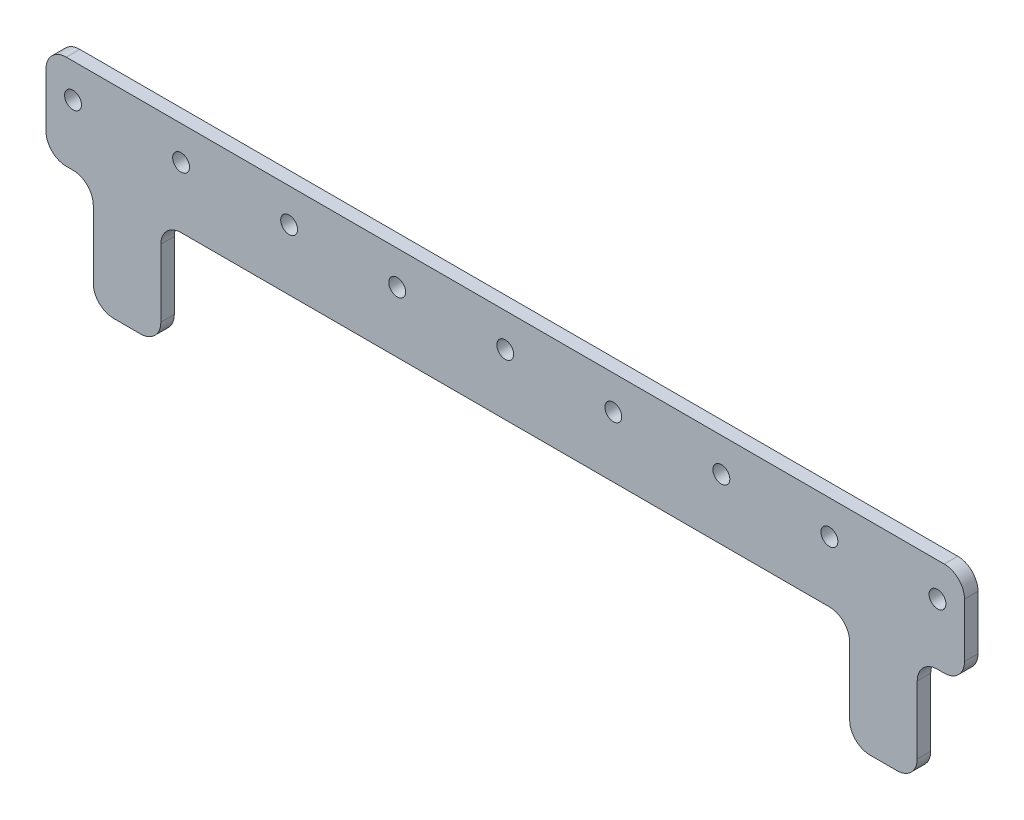
SolidWorks part; units mm, degrees
ref_plane "Top" through (0, 0, 0) normal (0, 0, 1) x (1, 0, 0)
ref_plane "Front" through (0, 0, 0) normal (0, 1, 0) x (1, 0, 0)
ref_plane "Right" through (0, 0, 0) normal (1, 0, 0) x (0, 0, -1)
sketch "Base Sketch" plane through (0, 0, 0) normal (0, 0, 1) x (1, 0, 0)
  line L0 (-68, 7) -> (68, -7) construction
  line L1 (-68, 7) -> (68, 7)
  line L2 (-68, 7) -> (-68, -7)
  line L3 (-68, -7) -> (68, -7)
  line L4 (68, 7) -> (68, -7)
  point P4 (0, 0)
  dimension "Length" = 136
  dimension "D2" = 14
extrude "Base Extrude" add sketch "Base Sketch" against normal blind 2
sketch "Pin Hole Sketch" plane through (0, 0, 0) normal (0, 0, 1) x (1, 0, 0)
  line L0 (68, -7) -> (68, 7) construction
  line L1 (68, 7) -> (-68, 7) construction
  circle A0 centre (64, 2) radius 1.25
  dimension "Diameter" = 2.5
  dimension "D1" = 4
  dimension "D2" = 5
extrude "First Pin Hole Cut" cut sketch "Pin Hole Sketch" against normal through all
pattern_linear "Pin Hole Pattern" count 9 spacing 16 along (-1, 0, 0) of "First Pin Hole Cut"
sketch "Extension Sketch" plane through (0, 0, 0) normal (0, 0, 1) x (1, 0, 0)
  line L0 (48, 2) -> (64, 2) construction
  line L1 (56, 2) -> (56, -23) construction
  line L2 (51, -23) -> (61, -23)
  line L3 (61, -23) -> (61, 2)
  line L4 (61, 2) -> (51, 2)
  line L5 (51, 2) -> (51, -23)
  line L6 (68, 7) -> (-68, 7) construction
  circle A0 centre (64, 2) radius 1.25 construction
  circle A1 centre (48, 2) radius 1.25 construction
  dimension "D1" = 10
  dimension "D2" = 30
extrude "Tab Extrude" add sketch "Extension Sketch" against normal through all separate body
mirror "Tab Mirror" about plane through (0, 0, 0) normal (1, 0, 0) of "Tab Extrude"
combine bodies "Combine Bodies" operation type add bodies to combine 106 105
fillet "Corner Fillets" radius 3 12 edges at (68, 7, -1) (68, -7, -1) (-68, -7, -1) (-68, 7, -1) (51, -7, -1) (-61, -7, -1) (-51, -7, -1) (61, -7, -1) (-61, -23, -1) (-51, -23, -1) (51, -23, -1) (61, -23, -1)
